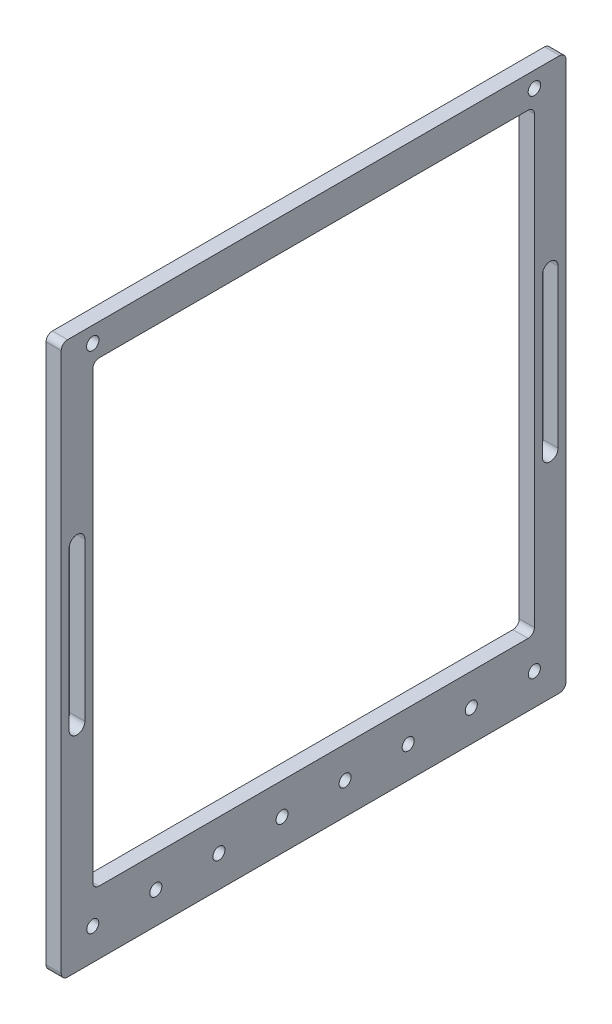
SolidWorks part; units mm, degrees
ref_plane "Front Plane" through (0, 0, 0) normal (0, 0, 1) x (1, 0, 0)
ref_plane "Top Plane" through (0, 0, 0) normal (0, 1, 0) x (1, 0, 0)
ref_plane "Right Plane" through (0, 0, 0) normal (1, 0, 0) x (0, 0, -1)
sketch "Sketch1" plane through (0, 0, 0) normal (1, 0, 0) x (0, 0, -1)
  line L1 (0, 0) -> (177.8, 0)
  line L2 (0, 0) -> (0, -184.15)
  line L3 (0, -184.15) -> (177.8, -184.15)
  line L4 (177.8, 0) -> (177.8, -184.15)
  line L5 (-12.7, 12.7) -> (190.5, 12.7)
  line L6 (-12.7, 12.7) -> (-12.7, -209.55)
  line L7 (-12.7, -209.55) -> (190.5, -209.55)
  line L8 (190.5, 12.7) -> (190.5, -209.55)
  circle A1 centre (0, -196.85) radius 2.425
  circle A2 centre (25.4, -196.85) radius 2.425
  circle A3 centre (50.8, -196.85) radius 2.425
  circle A4 centre (76.2, -196.85) radius 2.425
  circle A5 centre (101.6, -196.85) radius 2.425
  circle A6 centre (127, -196.85) radius 2.425
  circle A7 centre (152.4, -196.85) radius 2.425
  circle A8 centre (177.8, -196.85) radius 2.425
  point P10 (0, 0)
  dimension "D7" = 8
  dimension "D8" = 4.85
  dimension "D9" = 12.7
  dimension "D1" = 184.15
  dimension "D2" = 177.8
  dimension "D3" = 12.7
  dimension "D4" = 12.7
  dimension "D5" = 12.7
  dimension "D6" = 25.4
  dimension "D10" = 12.7
extrude "Boss-Extrude1" add sketch "Sketch1" along normal blind 6.096
fillet "Fillet1" radius 2.54 8 edges at (3.048, 12.7, -190.5) (3.048, 12.7, 12.7) (3.048, -209.55, -190.5) (3.048, -209.55, 12.7) (3.048, -184.15, 0) (3.048, -184.15, -177.8) (3.048, 0, -177.8) (3.048, 0, 0)
sketch "Sketch2" plane through (6.096, 0, 0) normal (1, 0, 0) x (0, 0, -1)
  line L0 (-6.35, -60.325) -> (-6.35, -123.825) construction
  line L1 (-3.175, -60.325) -> (-3.175, -123.825)
  line L2 (-9.525, -60.325) -> (-9.525, -123.825)
  line L6 (0, -2.54) -> (0, -181.61) construction
  line L7 (0, -92.075) -> (-12.7, -92.075) construction
  line L8 (-12.7, 10.16) -> (-12.7, -207.01) construction
  line L9 (88.9, 0) -> (88.9, -184.15) construction
  line L10 (175.26, 0) -> (2.54, 0) construction
  line L11 (2.54, -184.15) -> (175.26, -184.15) construction
  line L12 (184.15, -60.325) -> (184.15, -123.825) construction
  line L13 (180.975, -60.325) -> (180.975, -123.825)
  line L14 (187.325, -60.325) -> (187.325, -123.825)
  arc A0 (-3.175, -60.325) -> (-9.525, -60.325) centre (-6.35, -60.325) ccw
  arc A1 (-9.525, -123.825) -> (-3.175, -123.825) centre (-6.35, -123.825) ccw
  arc A4 (180.975, -60.325) -> (187.325, -60.325) centre (184.15, -60.325) cw
  arc A5 (187.325, -123.825) -> (180.975, -123.825) centre (184.15, -123.825) cw
  point P2 (-6.35, -92.075)
  point P14 (0, -92.075)
  point P21 (0, 0)
  point P26 (0, 0)
  point P31 (184.15, -92.075)
  dimension "D1" = 3.175
  dimension "D2" = 63.5
extrude "Cut-Extrude1" cut sketch "Sketch2" against normal through all
sketch "Sketch3" plane through (6.096, 0, 0) normal (1, 0, 0) x (0, 0, -1)
  line L0 (190.5, -207.01) -> (190.5, 10.16) construction
  line L1 (2.54, -184.15) -> (175.26, -184.15) construction
  line L2 (88.9, 12.7) -> (88.9, -209.55) construction
  line L3 (187.96, 12.7) -> (-10.16, 12.7) construction
  line L4 (-10.16, -209.55) -> (187.96, -209.55) construction
  circle A0 centre (177.8, 6.35) radius 2.505
  circle A1 centre (0, 6.35) radius 2.505
  dimension "D1" = 5.01
  dimension "D2" = 12.7
  dimension "D3" = 190.5
extrude "Cut-Extrude2" cut sketch "Sketch3" against normal through all both and the other way through all
